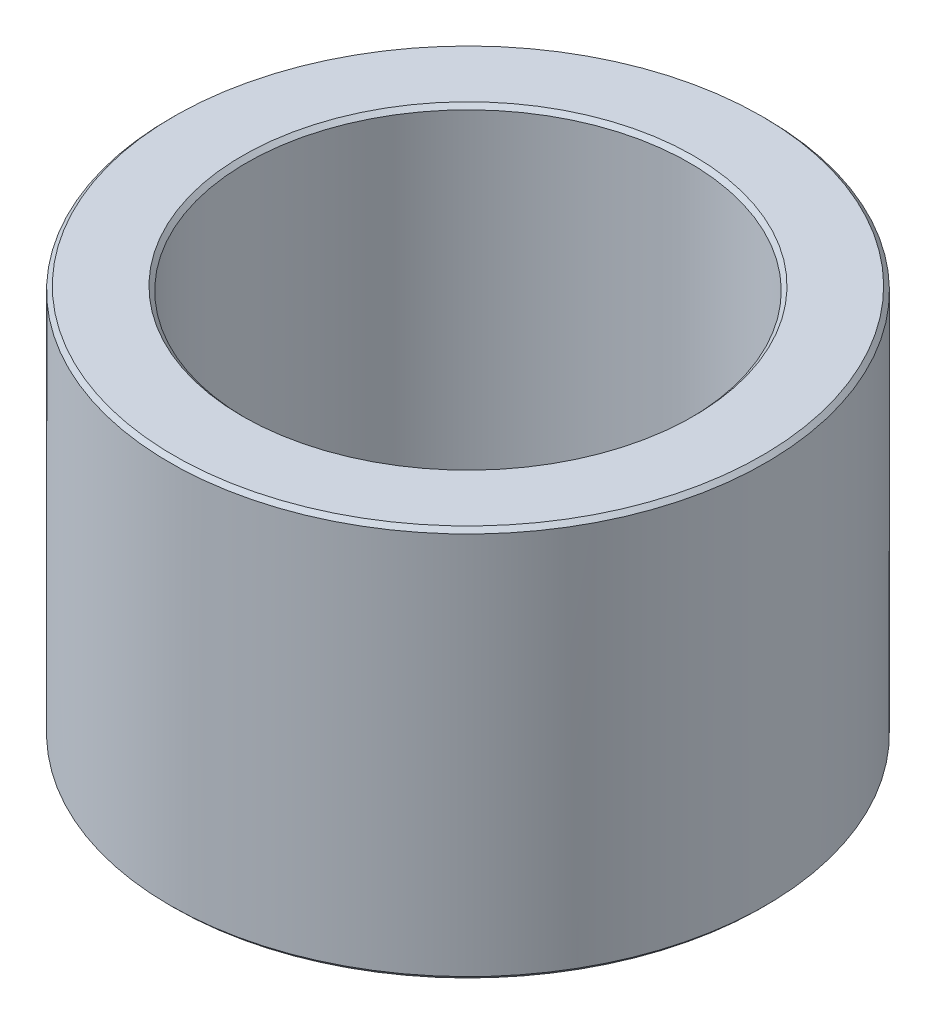
SolidWorks part; units mm, degrees
ref_plane "Front Plane" through (0, 0, 0) normal (0, 0, 1) x (1, 0, 0)
ref_plane "Top Plane" through (0, 0, 0) normal (0, 1, 0) x (1, 0, 0)
ref_plane "Right Plane" through (0, 0, 0) normal (1, 0, 0) x (0, 0, -1)
sketch "Sketch1" plane through (0, 0, 0) normal (0, 1, 0) x (1, 0, 0)
  circle A0 centre (0, 0) radius 30
  dimension "SLEEVE_OD" = 60
extrude "Boss-Extrude1" add sketch "Sketch1" along normal blind 39.4085
sketch "Sketch2" plane through (0, 0, 0) normal (0, 1, 0) x (1, 0, 0)
  circle A0 centre (0, 0) radius 22.3008
  dimension "BORE_D" = 44.6017
extrude "Cut-Extrude1" cut sketch "Sketch2" along normal through all
chamfer "Chamfer1" distance 0.4109 angle 45 4 edges at (0, 39.4085, 22.3008) (0, 0, 22.3008) (0, 0, 30) (0, 39.4085, 30)
